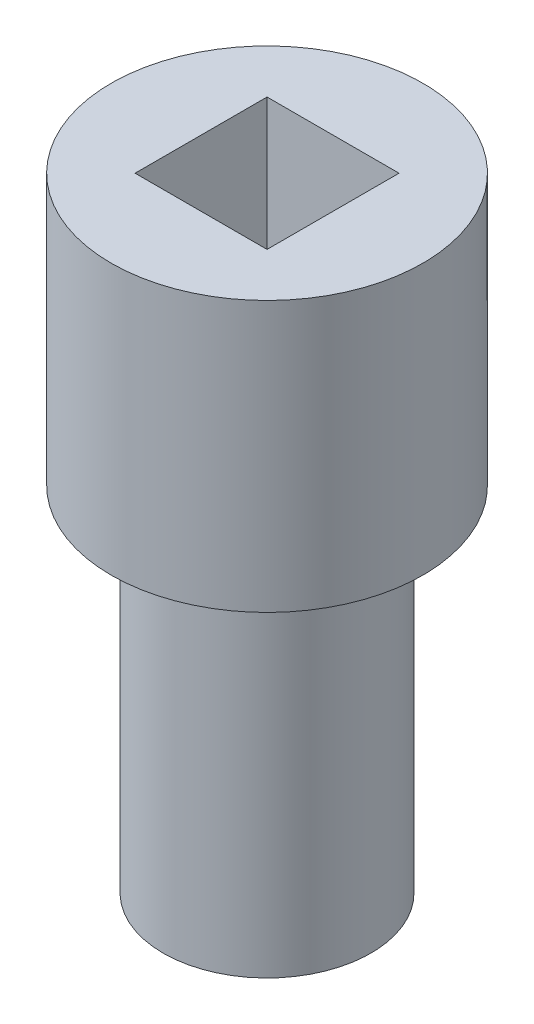
SolidWorks part; units mm, degrees
note: The reader was unsure of these and kept them because the rebuilt part matched: shared geometry of "Sketch2<4>", "Sketch2<5>".
ref_plane "Front Plane" through (0, 0, 0) normal (0, 0, 1) x (1, 0, 0)
ref_plane "Top Plane" through (0, 0, 0) normal (0, 1, 0) x (1, 0, 0)
ref_plane "Right Plane" through (0, 0, 0) normal (1, 0, 0) x (0, 0, -1)
sketch "Sketch2" plane through (0, 0, 0) normal (0, 1, 0) x (1, 0, 0)
  line L1 (-3.175, -3.175) -> (3.175, -3.175)
  line L2 (-3.175, -3.175) -> (-3.175, 3.175)
  line L3 (-3.175, 3.175) -> (3.175, 3.175)
  line L4 (3.175, -3.175) -> (3.175, 3.175)
  line L5 (-3.175, -3.175) -> (3.175, 3.175) construction
  line L6 (-3.175, 3.175) -> (3.175, -3.175) construction
  circle A0 centre (0, 0) radius 7.5
  circle A1 centre (0, 0) radius 5
  point P0 (0, 0)
  dimension "D2" = 15
  dimension "D3" = 10
  dimension "D1" = 6.35
extrude "Boss-Extrude1" add sketch "Sketch2" along normal blind 10 contours A1 L4 L1 L2 L3 | A0 A1
extrude "Boss-Extrude2" add sketch "Sketch2<4>" against normal blind 20 contours A0 L4 L1 L2 L3 | L1 L4 L3 L2 A1 | A1
sketch "Sketch2<4>" plane through (0, 0, 0) normal (0, 1, 0) x (1, 0, 0) same geometry as "Sketch2"
extrude "Boss-Extrude3" add sketch "Sketch2<5>" against normal blind 3 contours A0 A1
sketch "Sketch2<5>" plane through (0, 0, 0) normal (0, 1, 0) x (1, 0, 0) same geometry as "Sketch2"
sketch "Sketch3" plane through (0, -20, 0) normal (0, -1, 0) x (1, 0, 0)
  circle A0 centre (0, 0) radius 2
  dimension "D1" = 4
extrude "Cut-Extrude1" cut sketch "Sketch3" against normal blind 8.5
